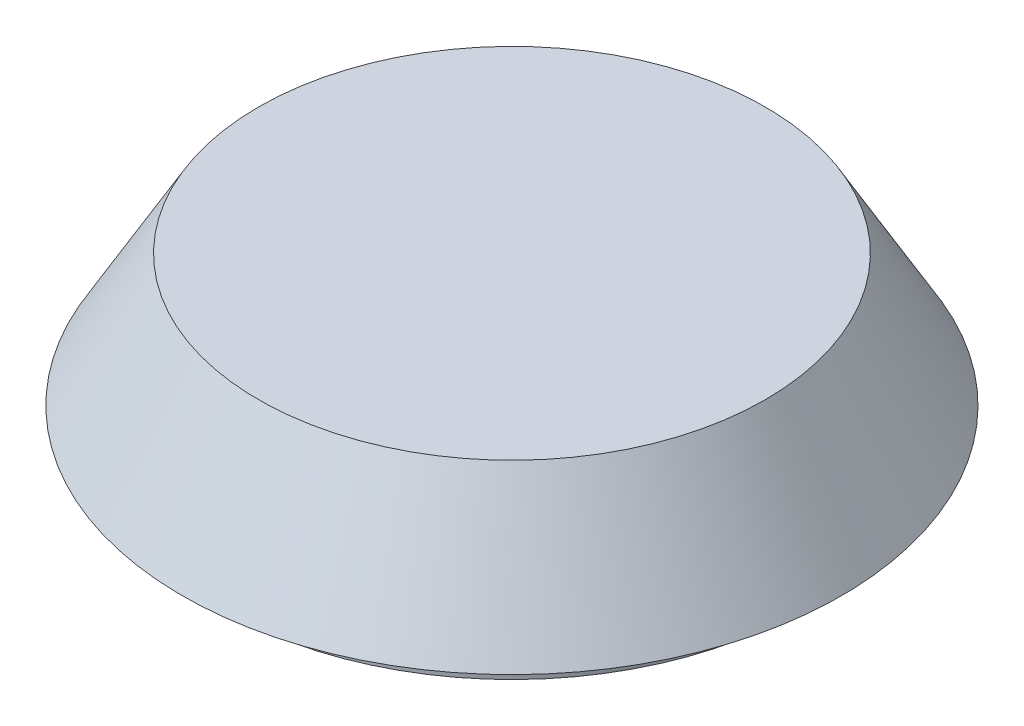
SolidWorks part; units mm, degrees
ref_plane "Front Plane" through (0, 0, 0) normal (0, 0, 1) x (1, 0, 0)
ref_plane "Top Plane" through (0, 0, 0) normal (0, 1, 0) x (1, 0, 0)
ref_plane "Right Plane" through (0, 0, 0) normal (1, 0, 0) x (0, 0, -1)
sketch "Sketch2" plane through (0, 0, 0) normal (0, 1, 0) x (1, 0, 0)
  circle A0 centre (0, 0) radius 43.85
  dimension "D1" = 87.7
extrude "Boss-Extrude1" add sketch "Sketch2" along normal blind 5
sketch "Sketch4" plane through (0, 0, 0) normal (0, 0, 1) x (1, 0, 0)
  line L0 (0, 5) -> (50, 5)
  line L1 (50, 5) -> (38.453, 25)
  line L2 (38.453, 25) -> (0, 25)
  line L3 (0, 25) -> (0, 5)
  dimension "D1" = 50
  dimension "D2" = 60
  dimension "D3" = 20
revolve "Revolve1" add sketch "Sketch4" angle 360 about L3
equation "\"D1@Sketch2\"=87.7"
